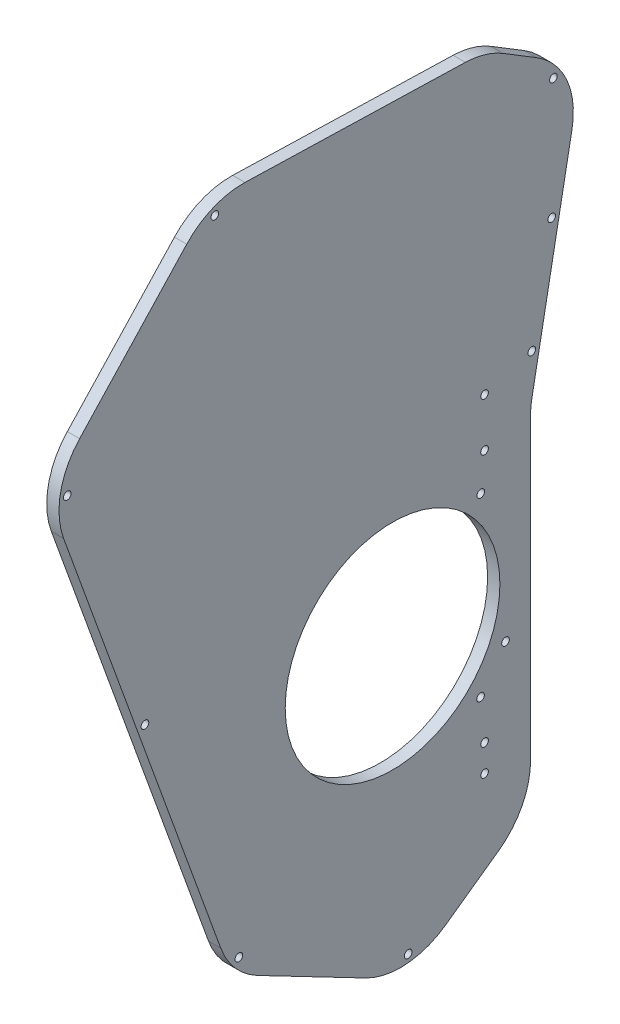
SolidWorks part; units mm, degrees
material "Zoltek Panex 33"
ref_plane "前视基准面" through (0, 0, 0) normal (0, 0, 1) x (1, 0, 0)
ref_plane "上视基准面" through (0, 0, 0) normal (0, 1, 0) x (1, 0, 0)
ref_plane "右视基准面" through (0, 0, 0) normal (1, 0, 0) x (0, 0, -1)
other "Configuration Table"
sketch "草图1" plane through (0, 0, 0) normal (0, 1, 0) x (1, 0, 0)
  line L0 (0, 0) -> (111.3, 0) construction
  line L1 (111.3, 0) -> (111.3, -10) construction
  line L2 (111.3, -10) -> (8, -10) construction
  line L3 (8, -10) -> (8, -300)
  line L4 (8, -300) -> (0, -300)
  line L5 (0, -300) -> (0, 0)
  line L6 (8, -10) -> (8, 0)
  line L7 (0, 0) -> (8, 0)
  dimension "D1" = 103.3
  dimension "D2" = 290
  dimension "D3" = 10
  dimension "D4" = 8
extrude "凸台-拉伸1" add sketch "草图1" along normal blind 180
sketch "草图2" plane through (8, 0, 0) normal (1, 0, 0) x (0, 0, -1)
  line L0 (-318.0541, 90) -> (-40.874, 90) construction
  line L1 (-300, 180) -> (0, 180) construction
  line L2 (-300, 0) -> (0, 0) construction
  line L3 (-90, 0) -> (-300, 0)
  line L4 (-300, 0) -> (-300, 180)
  line L5 (-300, 180) -> (-90, 180)
  line L7 (0, 180) -> (0, 0) construction
  arc A0 (-90, 180) -> (-90, 0) centre (-90, 90) ccw
  circle A1 centre (-90, 90) radius 70
  dimension "D2" = 140
  dimension "D1" = 90
extrude "切除-拉伸1" cut sketch "草图2" against normal blind 180
sketch "草图3" plane through (0, 0, 0) normal (-1, 0, 0) x (0, 0, 1)
  line L0 (0, 180) -> (-33.4481, 357.3687)
  line L1 (-33.4481, 357.3687) -> (29.1955, 395.566)
  line L3 (314.9515, 286.8152) -> (195.3561, -42.9636)
  line L4 (195.3561, -42.9636) -> (80.5757, -102.6908)
  line L6 (0, 0) -> (90, 0) construction
  line L7 (0, 180) -> (90, 180) construction
  line L8 (0, 0) -> (90, 0)
  line L9 (0, 180) -> (90, 180)
  line L10 (314.9515, 286.8152) -> (208.8377, 400.6164)
  line L11 (208.8377, 400.6164) -> (29.1955, 395.566)
  line L12 (0, 0) -> (0, -45.3218)
  line L13 (0, -45.3218) -> (80.5757, -102.6908)
  arc A0 (90, 0) -> (90, 180) centre (90, 90) ccw construction
  arc A1 (90, 0) -> (90, 180) centre (90, 90) ccw
  dimension "D12" = 45.3218
extrude "凸台-拉伸2" add sketch "草图3" against normal up to surface (8 mm away) up to face at (8, 90, 20)
fillet "圆角1" radius 50 8 edges at (4, 357.3687, -33.4481) (4, 395.566, 29.1955) (4, 400.6164, 208.8377) (4, 286.8152, 314.9515) (4, -42.9636, 195.3561) (4, -102.6908, 80.5757) (4, -45.3218, 0) (4, 180, 0)
sketch "草图4" plane through (8, 0, 0) normal (1, 0, 0) x (0, 0, -1)
  line L0 (0.866, 184.5924) -> (27.0434, 323.406) construction
  circle A0 centre (-205.8488, 391.166) radius 2.5
  circle A1 centre (-302.1195, 281.0491) radius 2.5
  circle A2 centre (-251.4598, 126.4058) radius 2.5
  circle A3 centre (-190.211, -35.6154) radius 2.5
  circle A4 centre (-79.8053, -88.9483) radius 2.5
  circle A5 centre (-30, 5.5773) radius 2.5
  circle A6 centre (-30, 202.0587) radius 2.5
  circle A7 centre (-30, 170.5483) radius 2.5
  circle A8 centre (-30, -11.97) radius 2.5
  circle A9 centre (14.8828, 358.3226) radius 2.5
  circle A10 centre (13.7706, 280.004) radius 2.5
  circle A11 centre (0.7986, 211.2164) radius 2.5
  circle A16 centre (-32.61, 32.4852) radius 2.5
  circle A17 centre (-16.3252, 55.7423) radius 2.5
  circle A18 centre (-32.4852, 147.39) radius 2.5
  dimension "D1" = 5
  dimension "D2" = 5
  dimension "D4" = 70
extrude "切除-拉伸2" cut sketch "草图4" against normal blind 40
